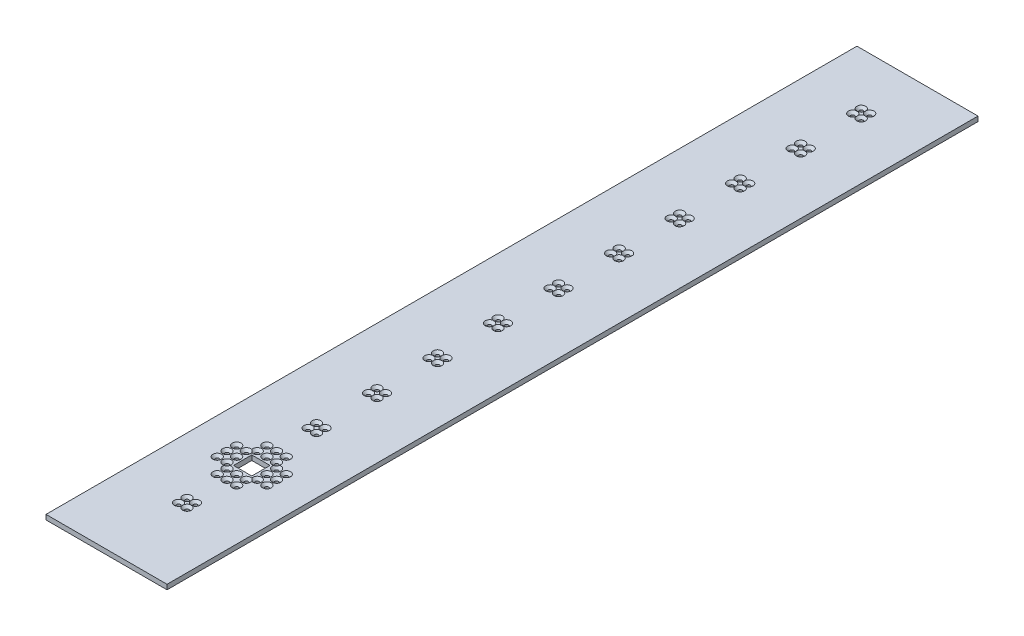
SolidWorks part; units mm, degrees
ref_plane "前视基准面" through (0, 0, 0) normal (0, 0, 1) x (1, 0, 0)
ref_plane "上视基准面" through (0, 0, 0) normal (0, 1, 0) x (1, 0, 0)
ref_plane "右视基准面" through (0, 0, 0) normal (1, 0, 0) x (0, 0, -1)
other "Configuration Table"
sketch "草图1" plane through (0, 0, 0) normal (0, 1, 0) x (1, 0, 0)
  line L0 (0, -215) -> (0, 0) construction
  line L1 (50, -335) -> (-50, -335)
  line L2 (50, -335) -> (50, 335)
  line L3 (50, 335) -> (-50, 335)
  line L4 (-50, -335) -> (-50, 335)
  line L5 (50, -335) -> (-50, 335) construction
  line L6 (50, 335) -> (-50, -335) construction
  line L7 (7.55, -222.55) -> (-7.55, -222.55)
  line L8 (7.55, -222.55) -> (7.55, -207.45)
  line L9 (7.55, -207.45) -> (-7.55, -207.45)
  line L10 (-7.55, -222.55) -> (-7.55, -207.45)
  line L11 (7.55, -222.55) -> (-7.55, -207.45) construction
  line L12 (7.55, -207.45) -> (-7.55, -222.55) construction
  line L13 (0, -215) -> (76.6567, -215) construction
  line L14 (7.5, -222.5) -> (-7.5, -222.5) construction
  line L15 (7.5, -222.5) -> (7.5, -207.5) construction
  line L16 (7.5, -207.5) -> (-7.5, -207.5) construction
  line L17 (-7.5, -222.5) -> (-7.5, -207.5) construction
  line L18 (7.5, -222.5) -> (-7.5, -207.5) construction
  line L19 (7.5, -207.5) -> (-7.5, -222.5) construction
  circle A0 centre (0, -202.5) radius 1.6
  circle A1 centre (0, -194.5) radius 1.6
  circle A2 centre (8, -194.5) radius 1.6
  circle A3 centre (8, -202.5) radius 1.6
  circle A4 centre (-8, -194.5) radius 1.6
  circle A5 centre (-8, -202.5) radius 1.6
  circle A6 centre (20.5, -207) radius 1.6
  circle A7 centre (12.5, -207) radius 1.6
  circle A8 centre (12.5, -215) radius 1.6
  circle A9 centre (20.5, -215) radius 1.6
  circle A10 centre (20.5, -223) radius 1.6
  circle A11 centre (12.5, -223) radius 1.6
  circle A12 centre (8, -235.5) radius 1.6
  circle A13 centre (8, -227.5) radius 1.6
  circle A14 centre (0, -227.5) radius 1.6
  circle A15 centre (0, -235.5) radius 1.6
  circle A16 centre (-8, -235.5) radius 1.6
  circle A17 centre (-8, -227.5) radius 1.6
  circle A18 centre (-20.5, -223) radius 1.6
  circle A19 centre (-12.5, -223) radius 1.6
  circle A20 centre (-12.5, -215) radius 1.6
  circle A21 centre (-20.5, -215) radius 1.6
  circle A22 centre (-20.5, -207) radius 1.6
  circle A23 centre (-12.5, -207) radius 1.6
  circle A24 centre (-3.5, -165) radius 1.6
  circle A25 centre (3.5, -165) radius 1.6
  circle A26 centre (-3.5, -158) radius 1.6
  circle A27 centre (3.5, -158) radius 1.6
  circle A28 centre (-3.5, -108) radius 1.6
  circle A29 centre (-3.5, -115) radius 1.6
  circle A30 centre (3.5, -115) radius 1.6
  circle A31 centre (3.5, -108) radius 1.6
  circle A32 centre (-3.5, -58) radius 1.6
  circle A33 centre (-3.5, -65) radius 1.6
  circle A34 centre (3.5, -65) radius 1.6
  circle A35 centre (3.5, -58) radius 1.6
  circle A36 centre (-3.5, -8) radius 1.6
  circle A37 centre (-3.5, -15) radius 1.6
  circle A38 centre (3.5, -15) radius 1.6
  circle A39 centre (3.5, -8) radius 1.6
  circle A40 centre (-3.5, 42) radius 1.6
  circle A41 centre (-3.5, 35) radius 1.6
  circle A42 centre (3.5, 35) radius 1.6
  circle A43 centre (3.5, 42) radius 1.6
  circle A44 centre (-3.5, 92) radius 1.6
  circle A45 centre (-3.5, 85) radius 1.6
  circle A46 centre (3.5, 85) radius 1.6
  circle A47 centre (3.5, 92) radius 1.6
  circle A48 centre (-3.5, 142) radius 1.6
  circle A49 centre (-3.5, 135) radius 1.6
  circle A50 centre (3.5, 135) radius 1.6
  circle A51 centre (3.5, 142) radius 1.6
  circle A52 centre (-3.5, 192) radius 1.6
  circle A53 centre (-3.5, 185) radius 1.6
  circle A54 centre (3.5, 185) radius 1.6
  circle A55 centre (3.5, 192) radius 1.6
  circle A56 centre (-3.5, 242) radius 1.6
  circle A57 centre (-3.5, 235) radius 1.6
  circle A58 centre (3.5, 235) radius 1.6
  circle A59 centre (3.5, 242) radius 1.6
  circle A60 centre (-3.5, 292) radius 1.6
  circle A61 centre (-3.5, 285) radius 1.6
  circle A62 centre (3.5, 285) radius 1.6
  circle A63 centre (3.5, 292) radius 1.6
  circle A64 centre (3.5, -265) radius 1.6
  circle A65 centre (3.5, -272) radius 1.6
  circle A66 centre (-3.5, -272) radius 1.6
  circle A67 centre (-3.5, -265) radius 1.6
  point P0 (0, 0)
  point P6 (0, -215)
  point P68 (0, -215)
  dimension "D6" = 3.2
  dimension "D12" = 3.2
  dimension "D1" = 100
  dimension "D2" = 670
  dimension "D3" = 15.1
  dimension "D4" = 120
  dimension "D5" = 15
  dimension "D7" = 5
  dimension "D8" = 8
  dimension "D13" = 50
  dimension "D14" = 3.5
  dimension "D9" = 2
  dimension "D10" = 2
  dimension "D15" = 2
  dimension "D16" = 10
  dimension "D11" = 4
extrude "凸台-拉伸1" add sketch "草图1" along normal blind 4
chamfer "倒角1" distance 2 angle 45 68 edges at (-8, 4, 204.1) (8, 4, 237.1) (12.5, 4, 216.6) (20.5, 4, 216.6) (12.5, 4, 224.6) (20.5, 4, 224.6) (12.5, 4, 208.6) (20.5, 4, 208.6) (8, 4, 229.1) (0, 4, 229.1) (0, 4, 237.1) (-8, 4, 237.1) (-8, 4, 229.1) (-12.5, 4, 224.6) (-20.5, 4, 224.6) (-12.5, 4, 216.6) (-20.5, 4, 216.6) (-20.5, 4, 208.6) (-12.5, 4, 208.6) (8, 4, 204.1) (0, 4, 204.1) (8, 4, 196.1) (0, 4, 196.1) (-8, 4, 196.1) (-3.5, 4, 166.6) (3.5, 4, 163.4) (-3.5, 4, 159.6) (3.5, 4, 156.4) (-3.5, 4, 116.6) (3.5, 4, 113.4) (-3.5, 4, 109.6) (3.5, 4, 106.4) (-3.5, 4, 66.6) (3.5, 4, 63.4) (-3.5, 4, 59.6) (3.5, 4, 56.4) (-3.5, 4, 16.6) (3.5, 4, 13.4) (-3.5, 4, 9.6) (3.5, 4, 6.4) (-3.5, 4, -33.4) (3.5, 4, -36.6) (-3.5, 4, -40.4) (3.5, 4, -43.6) (-3.5, 4, -83.4) (3.5, 4, -86.6) (-3.5, 4, -90.4) (3.5, 4, -93.6) (-3.5, 4, -133.4) (3.5, 4, -136.6) (-3.5, 4, -140.4) (3.5, 4, -143.6) (-3.5, 4, -183.4) (3.5, 4, -186.6) (-3.5, 4, -190.4) (3.5, 4, -193.6) (-3.5, 4, -233.4) (3.5, 4, -236.6) (-3.5, 4, -240.4) (3.5, 4, -243.6) (-3.5, 4, -283.4) (3.5, 4, -286.6) (-3.5, 4, -290.4) (3.5, 4, -293.6) (-3.5, 4, 270.4) (3.5, 4, 273.6) (3.5, 4, 266.6) (-3.5, 4, 263.4)
